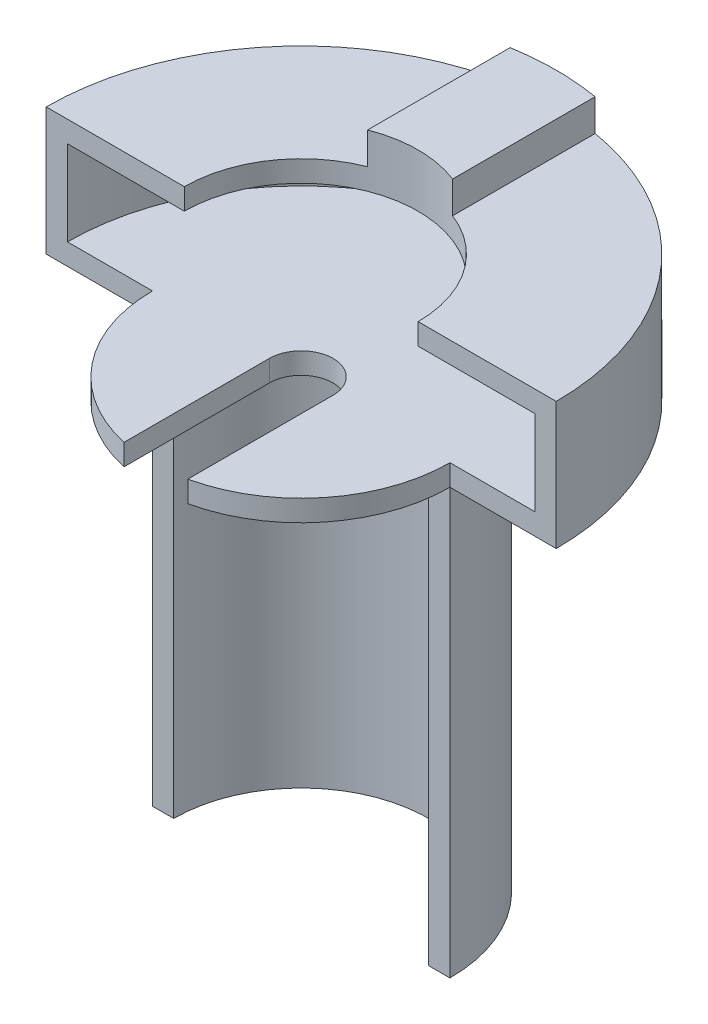
SolidWorks part; units mm, degrees
ref_plane "Front Plane" through (0, 0, 0) normal (0, 0, 1) x (1, 0, 0)
ref_plane "Top Plane" through (0, 0, 0) normal (0, 1, 0) x (1, 0, 0)
ref_plane "Right Plane" through (0, 0, 0) normal (1, 0, 0) x (0, 0, -1)
sketch "Sketch1" plane through (0, 0, 0) normal (0, 1, 0) x (1, 0, 0)
  line L0 (3, 0) -> (3, -13.6748)
  line L1 (-3, 0) -> (-3, -13.6748)
  line L2 (-14, 0) -> (-24, 0)
  line L3 (14, 0) -> (24, 0)
  circle A0 centre (0, 0) radius 14
  circle A1 centre (0, 0) radius 3
  arc A2 (24, 0) -> (-24, 0) centre (0, 0) ccw
  arc A3 (14, 0) -> (-14, 0) centre (0, 0) ccw
  dimension "D1" = 28
  dimension "D2" = 6
  dimension "D3" = 10
extrude "Motor-frontplate" add sketch "Sketch1" along normal blind 2 contours A1 L0 A0 L1 | L3 A2 L2 A3 region at (0, 0, -3.3937)
sketch "Sketch2" plane through (0, 0, 0) normal (0, -1, 0) x (1, 0, 0)
  line L2 (-12, 0) -> (-14, 0)
  line L3 (12, 0) -> (14, 0)
  arc A1 (-14, 0) -> (14, 0) centre (0, 0) ccw
  arc A3 (14, 0) -> (3, 13.6748) centre (0, 0) ccw construction
  arc A4 (-12, 0) -> (12, 0) centre (0, 0) ccw
  dimension "D1" = 2
extrude "Motorkrybbe" add sketch "Sketch2" along normal blind 40 contours A4 L3 A1 L2
sketch "Sketch5" plane through (0, 2, 0) normal (0, 1, 0) x (1, 0, 0)
  line L0 (-24, 0) -> (-22, 0)
  line L1 (24, 0) -> (22, 0)
  arc A1 (24, 0) -> (-24, 0) centre (0, 0) ccw construction
  arc A2 (22, 0) -> (-22, 0) centre (0, 0) ccw
  arc A3 (22, 0) -> (-22, 0) centre (0, 0) ccw
  arc A4 (24, 0) -> (-24, 0) centre (0, 0) ccw
  dimension "D1" = 2
extrude "Boss-Extrude4" add sketch "Sketch5" along normal blind 8 contours A3 L0 A4 L1
sketch "Sketch6" plane through (0, 10, 0) normal (0, 1, 0) x (1, 0, 0)
  line L0 (-24, 0) -> (-11, 0)
  line L1 (11, 0) -> (24, 0)
  arc A0 (-11, 0) -> (11, 0) centre (0, 0) cw
  arc A1 (24, 0) -> (-24, 0) centre (0, 0) ccw construction
  arc A2 (24, 0) -> (-24, 0) centre (0, 0) ccw
  dimension "D1" = 11
extrude "Boss-Extrude5" add sketch "Sketch6" along normal blind 2
sketch "Sketch7" plane through (0, 12, 0) normal (0, 1, 0) x (1, 0, 0)
  line L0 (-4, 10.247) -> (-4, 23.6643)
  line L1 (4, 23.6643) -> (4, 10.247)
  arc A0 (24, 0) -> (-24, 0) centre (0, 0) ccw construction
  arc A1 (11, 0) -> (-11, 0) centre (0, 0) ccw construction
  arc A2 (24, 0) -> (-24, 0) centre (0, 0) ccw
  arc A3 (11, 0) -> (-11, 0) centre (0, 0) ccw
  arc A4 (4, 10.247) -> (-4, 10.247) centre (0, 0) ccw
  arc A5 (4, 23.6643) -> (-4, 23.6643) centre (0, 0) ccw
  point P12 (0, 0)
  dimension "D1" = 4
  dimension "D2" = 4
extrude "Boss-Extrude6" add sketch "Sketch7" along normal blind 3 contours L1 A4 L0 A5
